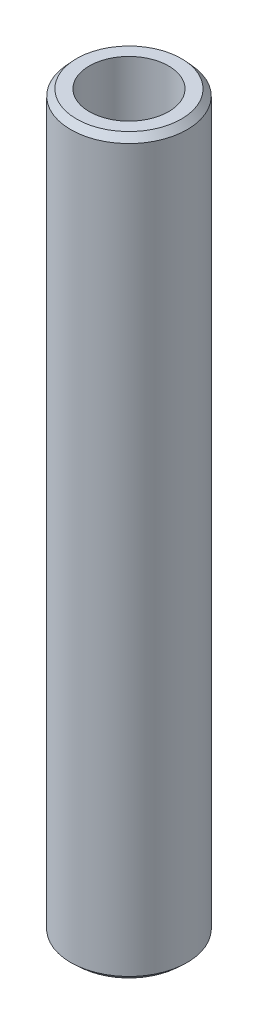
SolidWorks part; units mm, degrees
ref_plane "Front Plane" through (0, 0, 0) normal (0, 0, 1) x (1, 0, 0)
ref_plane "Top Plane" through (0, 0, 0) normal (0, 1, 0) x (1, 0, 0)
ref_plane "Right Plane" through (0, 0, 0) normal (1, 0, 0) x (0, 0, -1)
sketch "Sketch1" plane through (0, 0, 0) normal (0, 1, 0) x (1, 0, 0)
  circle A0 centre (0, 0) radius 17.5
  dimension "SHAFT_OD" = 35
extrude "Boss-Extrude1" add sketch "Sketch1" along normal blind 220.51
sketch "Sketch2" plane through (0, 0, 0) normal (0, 1, 0) x (1, 0, 0)
  circle A0 centre (0, 0) radius 11.9228
  dimension "BORE_D" = 23.8456
extrude "Cut-Extrude1" cut sketch "Sketch2" along normal through all
chamfer "Chamfer1" distance 1.895 angle 42.587 2 edges at (0, 220.51, 17.5) (0, 0, 17.5) first distance on face at (0, 220.51, 17.5) first distance on face at (0, 0, 11.9228)
